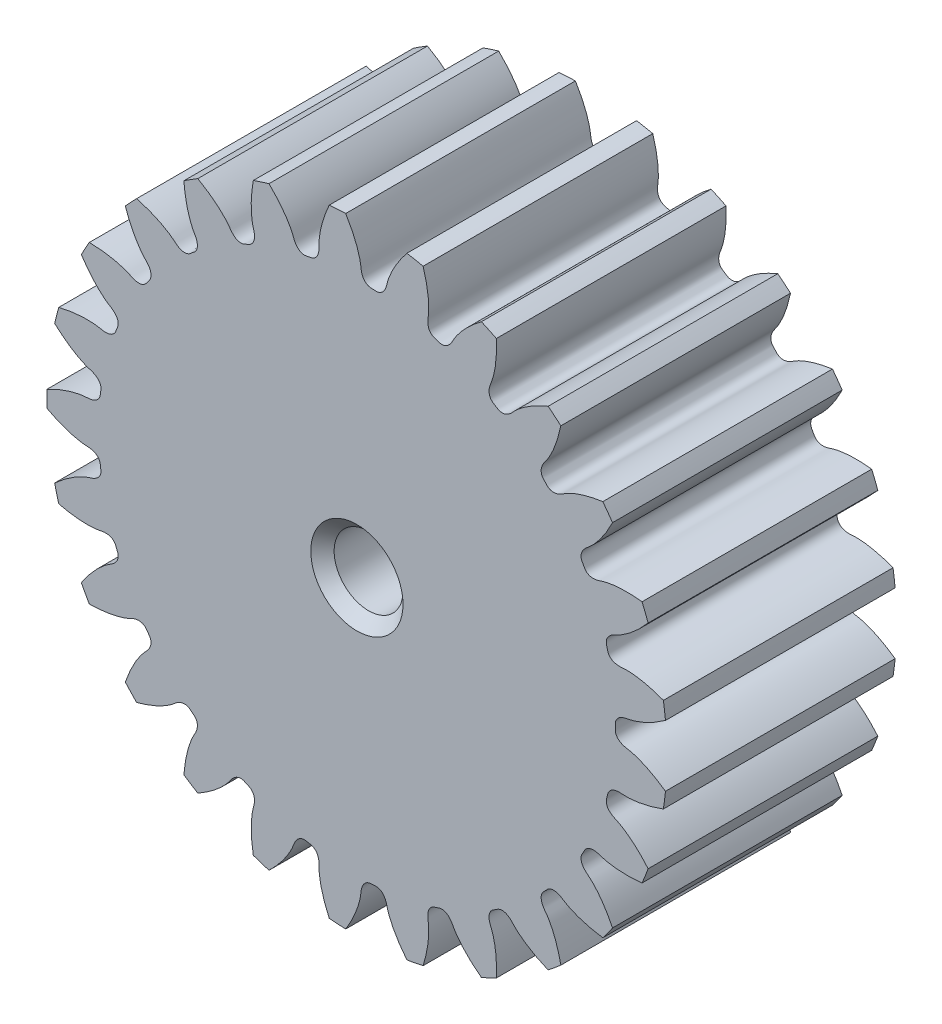
SolidWorks part; units mm, degrees
ref_plane "Front" through (0, 0, 0) normal (0, 0, 1) x (1, 0, 0)
ref_plane "Top" through (0, 0, 0) normal (0, 1, 0) x (1, 0, 0)
ref_plane "Right" through (0, 0, 0) normal (1, 0, 0) x (0, 0, -1)
ref_axis "Ось1" through (0, 0, 50) along (0, 0, -1)
sketch "SketchRevolvePlanet_Revolving_Follower01" plane through (0, 0, 0) normal (1, 0, 0) x (0, 0, -1)
  line L0 (0, 0) -> (1, 0) construction
  line L1 (-2.5, 0) -> (-2.5, 6.75)
  line L2 (-2.5, 6.75) -> (2.5, 6.75)
  line L3 (2.5, 6.75) -> (2.5, 0)
  line L4 (2.5, 0) -> (-2.5, 0)
  dimension "Side1" = 2.5
  dimension "OutsideRadius" = 6.75
  dimension "Side2" = 2.5
revolve "Planet_Revolving_Follower01" add sketch "SketchRevolvePlanet_Revolving_Follower01" angle 360 about L0
sketch "SketchToothPlanet_Revolving_Follower01" plane through (0, 0, 0) normal (0, 0, 1) x (1, 0, 0)
  arc A0 (6.7404, 0.6839) -> (6.7404, -0.6839) centre (0, 0) cw
  spline S0 degree 3 poles (6.7404, -0.6839) (6.6904, -0.648) (6.6161, -0.5976) (6.5168, -0.5365) (6.4474, -0.4965) (6.3811, -0.4608) (6.3182, -0.4292) (6.2587, -0.4015) (6.203, -0.3774) (6.1511, -0.3567) (6.1033, -0.3392) (6.0595, -0.3246) (6.02, -0.3127) (5.9848, -0.3031) (5.9541, -0.2958) (5.9121, -0.2868) (5.8752, -0.2819) (5.8431, -0.2745) (5.8294, -0.271) (5.816, -0.2671) (5.8029, -0.263) (5.7901, -0.2584) (5.7775, -0.2535) (5.7651, -0.2481) (5.7528, -0.2423) (5.7408, -0.2359) (5.7288, -0.2288) (5.717, -0.2211) (5.7054, -0.2124) (5.6938, -0.2028) (5.6824, -0.1921) (5.6713, -0.1799) (5.6607, -0.1663) (5.6507, -0.1509) (5.6417, -0.1337) (5.6342, -0.1148) (5.6285, -0.0942) (5.6254, -0.0738) (5.6241, -0.0422) (5.6257, 0) (5.6241, 0.0422) (5.6254, 0.0738) (5.6285, 0.0942) (5.6342, 0.1148) (5.6417, 0.1337) (5.6507, 0.1509) (5.6607, 0.1663) (5.6713, 0.1799) (5.6824, 0.1921) (5.6938, 0.2028) (5.7054, 0.2124) (5.717, 0.2211) (5.7288, 0.2288) (5.7408, 0.2359) (5.7528, 0.2423) (5.7651, 0.2481) (5.7775, 0.2535) (5.7901, 0.2584) (5.8029, 0.263) (5.816, 0.2671) (5.8294, 0.271) (5.8431, 0.2745) (5.8752, 0.2819) (5.9121, 0.2868) (5.9541, 0.2958) (5.9848, 0.3031) (6.02, 0.3127) (6.0595, 0.3246) (6.1033, 0.3392) (6.1511, 0.3567) (6.203, 0.3774) (6.2587, 0.4015) (6.3182, 0.4292) (6.3811, 0.4608) (6.4474, 0.4965) (6.5168, 0.5365) (6.6161, 0.5976) (6.6904, 0.648) (6.7404, 0.6839) knots 0 0 0 0 0.066592 0.09726 0.126175 0.153338 0.178748 0.202406 0.224312 0.244465 0.262865 0.279513 0.294409 0.307552 0.318943 0.328581 0.35401 0.359185 0.364277 0.369297 0.374256 0.379169 0.384052 0.388923 0.393806 0.398725 0.40371 0.408794 0.414018 0.419423 0.425056 0.430965 0.437198 0.443793 0.450773 0.458134 0.46584 0.473813 0.480451 0.5 0.519549 0.526187 0.53416 0.541866 0.549227 0.556207 0.562802 0.569035 0.574944 0.580577 0.585982 0.591206 0.59629 0.601275 0.606194 0.611077 0.615948 0.620831 0.625744 0.630703 0.635723 0.640815 0.64599 0.671419 0.681057 0.692448 0.705591 0.720487 0.737135 0.755535 0.775688 0.797594 0.821252 0.846662 0.873825 0.90274 0.933408 1 1 1 1
extrude "ToothExtrudeCutPlanet_Revolving_Follower01" cut sketch "SketchToothPlanet_Revolving_Follower01" against normal blind 2.5 and the other way blind 2.5
ref_axis "Ось2" through (80.9, 0, 0) along (-1, 0, 0)
ref_plane "Плоскость1" through (0, 0, 0) normal (0, 0, -1) x (1, 0, 0)
pattern_circular "PatternPlanet_Revolving_Follower01" count 25 every 14.4 about axis through (0, 0, 50) along (0, 0, -1) of "ToothExtrudeCutPlanet_Revolving_Follower01"
sketch "BoreRevolveSketch" plane through (0, 0, 0) normal (1, 0, 0) x (0, 0, -1)
  line L0 (0, 0) -> (1, 0) construction
  line L1 (-2.5, 0) -> (2.5, 0)
  line L2 (2.5, 0) -> (2.5, 1.004)
  line L3 (2.5, 1.004) -> (2.246, 0.75)
  line L4 (2.246, 0.75) -> (-2.246, 0.75)
  line L5 (-2.246, 0.75) -> (-2.5, 1.004)
  line L6 (-2.5, 1.004) -> (-2.5, 0)
  dimension "BoreSide1" = 2.5
  dimension "TaperSide1" = 1.004
  dimension "Chamfer1X" = 0.254
  dimension "Chamfer1Y" = 0.254
  dimension "BoreSide2" = 2.5
  dimension "TaperSide2" = 1.004
revolve "BoreRevolveCut" cut sketch "BoreRevolveSketch" angle 360 about L0
sketch "KeywaySketch" plane through (0, 0, 0) normal (0, 0, 1) x (1, 0, 0)
  line L0 (0, 0) -> (1.5, 0) construction
sketch "AuxiliarySketchPlanet_Revolving_Follower01" plane through (0, 0, 0) normal (0, 0, 1) x (1, 0, 0)
  circle A0 centre (0, 0) radius 6.25 construction
  circle A1 centre (0, 0) radius 5.8731 construction
  circle A2 centre (0, 0) radius 5.9035 construction
  circle A3 centre (0, 0) radius 6.75 construction
  circle A4 centre (0, 0) radius 5.625 construction
  dimension "PitchDiameter" = 12.5
  dimension "BaseDiameter" = 11.7462
  dimension "FormDiameter" = 11.8071
  dimension "MajorDiameter" = 13.5
  dimension "MinorDiameter" = 11.25
